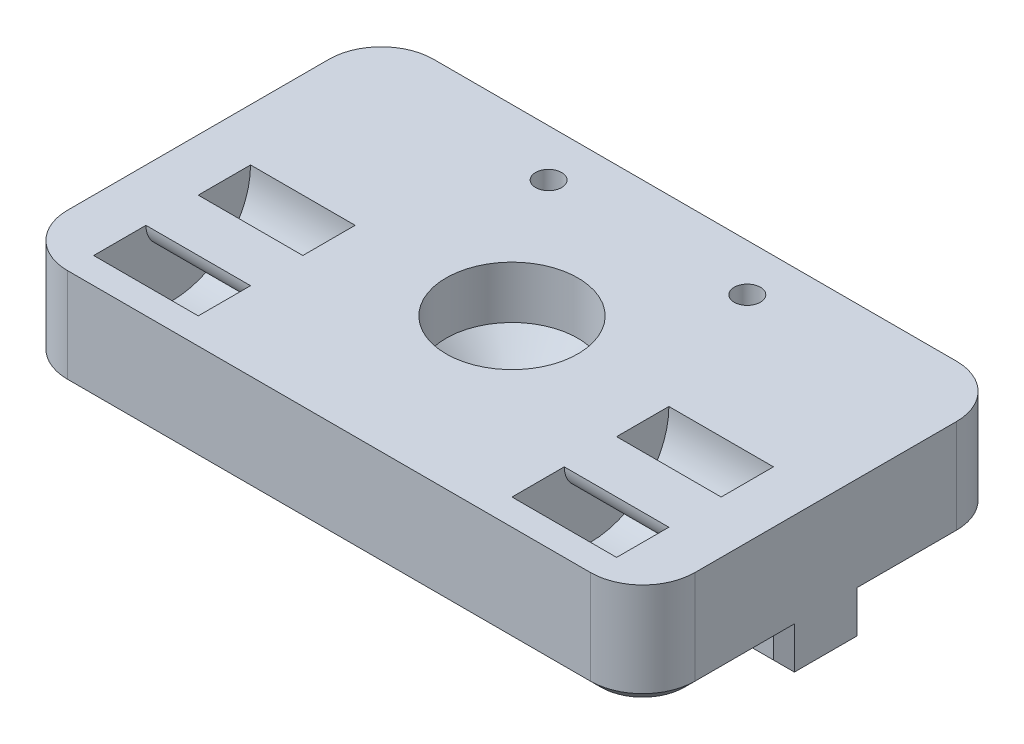
SolidWorks part; units mm, degrees
material "ABS"
ref_plane "Front Plane" through (0, 0, 0) normal (0, 0, 1) x (1, 0, 0)
ref_plane "Top Plane" through (0, 0, 0) normal (0, 1, 0) x (1, 0, 0)
ref_plane "Right Plane" through (0, 0, 0) normal (1, 0, 0) x (0, 0, -1)
sketch "Sketch1" plane through (0, 0, 0) normal (1, 0, 0) x (0, 0, -1)
  line L0 (-17.5, 10) -> (17.5, 10)
  line L1 (17.5, 10) -> (17.5, 0)
  line L2 (17.5, 0) -> (4, 0)
  line L3 (4, 0) -> (4, -3)
  line L4 (4, -3) -> (-4, -3)
  line L5 (-4, -3) -> (-4, 0)
  line L6 (-4, 0) -> (-17.5, 0)
  line L7 (-17.5, 0) -> (-17.5, 10)
  dimension "D1" = 17.5
  dimension "D2" = 17.5
  dimension "D3" = 8
  dimension "D4" = 3
  dimension "D5" = 10
extrude "Boss-Extrude1" add sketch "Sketch1" along normal mid plane 60
hole_wizard "CSK for M6 Flat Head Machine Screw1" positions "Sketch2" profile "Sketch3" countersink size "M6" standard "ANSI Metric" end condition up to next
sketch "Sketch2" plane through (0, 10, 0) normal (0, 1, 0) x (1, 0, 0)
  point P0 (0, 0)
sketch "Sketch3" plane through (0, 10, 0) normal (1, 0, 0) x (0, 0, 1)
  line L0 (0, 0) -> (0, 13)
  line L1 (0, 13) -> (3.3, 13)
  line L2 (3.3, 13) -> (3.3, 8)
  line L3 (3.3, 8) -> (6.3, 5)
  line L4 (6.3, 5) -> (6.3, 0)
  line L6 (6.3, 0) -> (0, 0)
  line L7 (-3.3, 8) -> (-6.3, 5) construction
  line L11 (0, -6.35) -> (0, 107.95) construction
  dimension "Thru Hole Dia." = 6.6
  dimension "Thru Hole Depth" = 13
  dimension "C'Sink Dia." = 12.6
  dimension "C'Sink Angle" = 90
  dimension "Head Clearance" = 5
ref_plane "Plane1" through (20, 0, 0) normal (1, 0, 0) x (0, 0, -1)
sketch "Sketch4" plane through (20, 0, 0) normal (1, 0, 0) x (0, 0, -1)
  line L0 (-15, 10) -> (-10, 10)
  line L1 (17.5, 10) -> (-17.5, 10) construction
  line L2 (-5, 10) -> (0, 10)
  arc A0 (-10, 10) -> (-5, 10) centre (-7.5, 10) ccw
  arc A1 (-15, 10) -> (0, 10) centre (-7.5, 10) ccw
  point P8 (-12.5, 10)
  dimension "D1" = 5
  dimension "D2" = 7.5
  dimension "D3" = 5
extrude "Cut-Extrude1" cut sketch "Sketch4" against normal mid plane 10
mirror "Mirror1" about plane through (0, 0, 0) normal (1, 0, 0) of "Cut-Extrude1"
fillet "Fillet1" radius 5 4 edges at (30, 5, 17.5) (30, 5, -17.5) (-30, 5, 17.5) (-30, 5, -17.5)
chamfer "Chamfer1" distance 1 angle 45 16 edges at (0, 0, 17.5) (0, 0, -17.5) (0, -3, 4) (0, -3, -4) (30, 0, 8.25) (-30, 0, 8.25) (28.5355, 0, 16.0355) (-28.5355, 0, 16.0355) (30, 0, -8.25) (-30, 0, -8.25) (28.5355, 0, -16.0355) (-28.5355, 0, -16.0355) (30, -1.5, 4) (-30, -1.5, 4) (30, -1.5, -4) (-30, -1.5, -4)
hole_wizard "M3x0.5 Tapped Hole1" positions "Sketch5" profile "Sketch6" tap size "M3x0.5" standard "ANSI Metric" end condition up to next
sketch "Sketch5" plane through (0, 10, 0) normal (0, 1, 0) x (1, 0, 0)
  line L0 (-9.5, 13) -> (9.5, 13)
  line L2 (0, -7.15) -> (0, 7.15) construction
  point P0 (-9.5, 13)
  point P2 (9.5, 13)
  point P10 (0, 13)
  dimension "D1" = 19
  dimension "D2" = 13
sketch "Sketch6" plane through (-9.5, 10, -13) normal (1, 0, 0) x (0, 0, 1)
  line L0 (0, 0) -> (0, 10)
  line L1 (0, 10) -> (1.25, 10)
  line L2 (1.25, 10) -> (1.25, 0)
  line L5 (1.25, 0) -> (0, 0)
  line L11 (0, -6.35) -> (0, 107.95) construction
  dimension "Thru Tap Drill Dia." = 2.5
  dimension "Thru Tap Drill Depth" = 10
cosmetic thread "Hole Thread1" parameters "D2"=3
cosmetic thread "Hole Thread2" parameters "D2"=3
